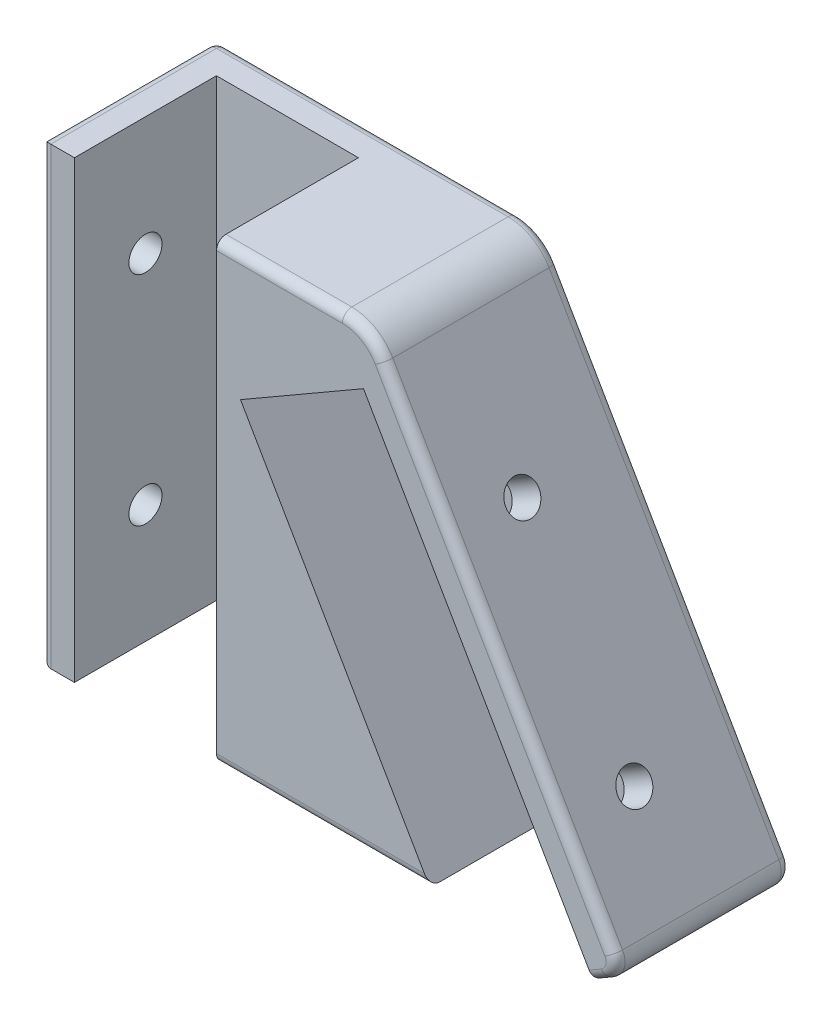
SolidWorks part; units mm, degrees
ref_plane "Front Plane" through (0, 0, 0) normal (0, 0, 1) x (1, 0, 0)
ref_plane "Top Plane" through (0, 0, 0) normal (0, 1, 0) x (1, 0, 0)
ref_plane "Right Plane" through (0, 0, 0) normal (1, 0, 0) x (0, 0, -1)
sketch "Sketch1" plane through (0, 0, 0) normal (0, 0, 1) x (1, 0, 0)
  line L0 (20.5456, 15.4888) -> (48.2584, -32.5112)
  line L2 (-14.145, 15.4888) -> (-14.145, -32.5112)
  line L3 (-14.145, -32.5112) -> (7.855, -32.5112)
  line L4 (7.855, 37.4696) -> (7.855, -32.5112) construction
  line L5 (48.2584, -32.5112) -> (7.855, -32.5112)
  line L6 (22.855, -32.5112) -> (7.855, -6.5304) construction
  line L7 (7.855, -6.5304) -> (45.9934, 15.4888) construction
  line L8 (20.5456, 15.4888) -> (-14.145, 15.4888)
  dimension "D2" = 30
  dimension "D3" = 22
  dimension "D4" = 30
  dimension "D5" = 48
extrude "Boss-Extrude1" add sketch "Sketch1" along normal blind 18.5
sketch "Sketch2" plane through (0, 0, 18.5) normal (0, 0, 1) x (1, 0, 0)
  line L1 (-14.145, -32.5112) -> (48.2584, -32.5112) construction
  line L2 (-10.645, 15.4888) -> (4.355, 15.4888)
  line L3 (-10.645, 15.4888) -> (-10.645, -32.5112)
  line L4 (-10.645, -32.5112) -> (4.355, -32.5112)
  line L5 (4.355, 15.4888) -> (4.355, -32.5112)
  line L6 (-14.145, 15.4888) -> (-14.145, -32.5112) construction
  line L7 (44.2169, -32.5112) -> (19.8868, 9.6298)
  line L8 (19.8868, 9.6298) -> (6.8964, 2.1298)
  line L9 (6.8964, 2.1298) -> (26.8964, -32.5112)
  line L10 (26.8964, -32.5112) -> (44.2169, -32.5112)
  line L11 (48.2584, -32.5112) -> (20.5456, 15.4888) construction
  line L12 (20.5456, 15.4888) -> (-14.145, 15.4888) construction
  dimension "D1" = 15
  dimension "D2" = 3.5
  dimension "D3" = 3.5
  dimension "D4" = 15
  dimension "D5" = 40
extrude "Cut-Extrude1" cut sketch "Sketch2" against normal offset from surface (15 mm away) 3.5 up to face at (10.1285, -8.5112, 0)
sketch "Sketch3" plane through (22.116, 12.7687, 0) normal (0.866, 0.5, 0) x (0, 0, -1)
  line L0 (-11, 30.2721) -> (-11, -52.2847) construction
  line L1 (-3.5, -1.6038) -> (-18.5, -1.6038) construction
  line L2 (-18.5, -52.2847) -> (0, -52.2847) construction
  line L3 (-3.5, -50.264) -> (-18.5, -50.264) construction
  circle A0 centre (-11, -37.764) radius 1.75
  circle A2 centre (-11, -14.1038) radius 1.75
  dimension "D1" = 3.5
  dimension "D2" = 12.5
  dimension "D3" = 12.5
extrude "Cut-Extrude2" cut sketch "Sketch3" against normal blind 3.5
sketch "Sketch4" plane through (0, 0, 0) normal (0, 0, -1) x (-1, 0, 0)
  line L0 (3.145, 15.4888) -> (3.145, -32.5112) construction
  line L2 (14.145, -32.5112) -> (-48.2584, -32.5112) construction
  line L3 (-13.3916, 5.8798) -> (-35.5567, -32.5112) construction
  line L4 (-6.8964, 2.1298) -> (-19.8868, 9.6298) construction
  line L5 (10.645, 15.4888) -> (-4.355, 15.4888) construction
  circle A0 centre (-29.3067, -21.6859) radius 1.75
  circle A2 centre (-19.6416, -4.9455) radius 1.75
  circle A4 centre (3.145, 2.9888) radius 1.75
  circle A6 centre (3.145, -20.0112) radius 1.75
  circle A7 centre (3.145, 14.4888) radius 1.75 [skipped]
  circle A8 centre (3.145, -8.5112) radius 1.75 [skipped]
  dimension "D1" = 12.5
  dimension "D2" = 12.5
  dimension "D4" = 3.5
  dimension "D5" = 4
  dimension "D6" = 12.5
  dimension "D7" = 12.5
extrude "Cut-Extrude3" cut sketch "Sketch4" against normal blind 4
sketch "Sketch5" plane through (-14.145, 0, 0) normal (-1, 0, 0) x (0, 0, 1)
  line L0 (11, 15.4888) -> (11, -32.5112) construction
  line L2 (18.5, -32.5112) -> (0, -32.5112) construction
  line L3 (18.5, 15.4888) -> (18.5, -32.5112) construction
  line L4 (18.5, 15.4888) -> (0, 15.4888) construction
  circle A0 centre (11, -20.0112) radius 1.75
  circle A2 centre (11, 2.9888) radius 1.75
  circle A4 centre (11, 14.4888) radius 1.75 [skipped]
  circle A5 centre (11, -8.5112) radius 1.75 [skipped]
  dimension "D2" = 3.5
  dimension "D3" = 12.5
  dimension "D5" = 12.5
  dimension "D1" = 7.5
  dimension "D4" = 4
extrude "Cut-Extrude4" cut sketch "Sketch5" against normal blind 4
sketch "Sketch6" plane through (0, 0, 18.5) normal (0, 0, 1) x (1, 0, 0)
  line L0 (44.2169, -32.5112) -> (47.248, -30.7612)
  line L1 (48.2584, -32.5112) -> (20.5456, 15.4888) construction
  line L2 (47.248, -30.7612) -> (48.2584, -32.5112)
  line L3 (48.2584, -32.5112) -> (44.2169, -32.5112)
extrude "Cut-Extrude5" cut sketch "Sketch6" against normal blind 19
fillet "Fillet1" radius 2 1 edges at (47.248, -30.7612, 9.25)
fillet "Fillet2" radius 5 1 edges at (20.5456, 15.4888, 9.25)
fillet "Fillet3" radius 1 16 edges at (44.8665, -32.1362, 18.5) (46.4478, -30.5468, 18.5) (34.1185, -8.0202, 18.5) (20.1588, 14.8189, 18.5) (44.8665, -32.1362, 0) (46.4478, -30.5468, 0) (34.1185, -8.0202, 0) (20.1588, 14.8189, 0) (15.6257, -32.5112, 18.5) (11.0069, 15.4888, 18.5) (-14.145, -32.5112, 9.25) (-14.145, 15.4888, 9.25) (-14.145, -8.5112, 18.5) (15.036, -32.5112, 0) (1.7569, 15.4888, 0) (-14.145, -8.5112, 0)
